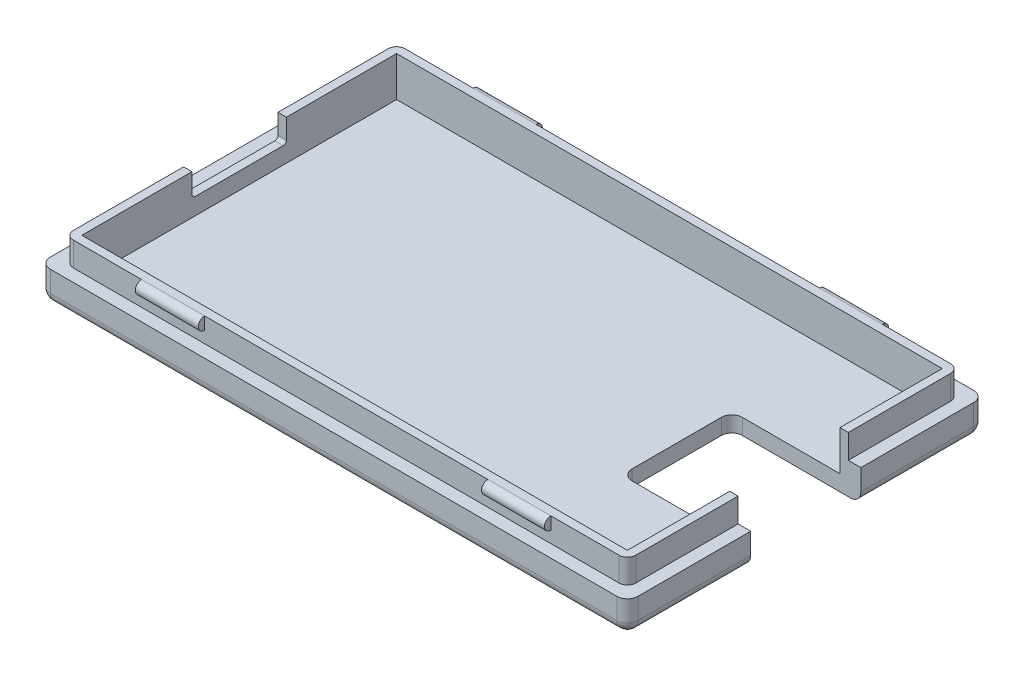
SolidWorks part; units mm, degrees
material "ABS"
ref_plane "Front Plane" through (0, 0, 0) normal (0, 0, 1) x (1, 0, 0)
ref_plane "Top Plane" through (0, 0, 0) normal (0, 1, 0) x (1, 0, 0)
ref_plane "Right Plane" through (0, 0, 0) normal (1, 0, 0) x (0, 0, -1)
sketch "Sketch1" plane through (0, 0, 0) normal (0, 1, 0) x (1, 0, 0)
  line L1 (28, -17) -> (-28, -17)
  line L2 (28, -17) -> (28, 17)
  line L3 (28, 17) -> (-28, 17)
  line L4 (-28, -17) -> (-28, 17)
  line L5 (28, -17) -> (-28, 17) construction
  line L6 (28, 17) -> (-28, -17) construction
  line L7 (26, -15) -> (-26, -15)
  line L8 (26, -15) -> (26, 15)
  line L9 (26, 15) -> (-26, 15)
  line L10 (-26, -15) -> (-26, 15)
  line L11 (26, -15) -> (-26, 15) construction
  line L12 (26, 15) -> (-26, -15) construction
  point P0 (0, 0)
  point P6 (0, 0)
  dimension "D1" = 56
  dimension "D2" = 34
  dimension "D3" = 2
  dimension "D4" = 2
extrude "Base" add sketch "Sketch1" along normal blind 1.5 contours L10 L7 L8 L9 | L4 L1 L2 L3 L7 L10 L9 L8 region at (0, 0, 16.3449) region at (0, 0, 0)
extrude "Boss-Extrude2" add sketch "Sketch1<3>" along normal blind 3 contours L4 L1 L2 L3 L7 L10 L9 L8 region at (0, 0, 16.3449)
sketch "Sketch1<3>" plane through (0, 0, 0) normal (0, 1, 0) x (1, 0, 0) same geometry as "Sketch1"
sketch "Sketch2" plane through (0, 3, 0) normal (0, 1, 0) x (1, 0, 0)
  line L0 (26, 15) -> (26, -15) construction
  line L1 (-26, -15) -> (26, -15) construction
  line L2 (-26, -15) -> (-26, 15) construction
  line L3 (-26, 15) -> (26, 15) construction
  line L4 (26, 15) -> (26, -15)
  line L5 (-26, -15) -> (26, -15)
  line L6 (-26, -15) -> (-26, 15)
  line L7 (-26, 15) -> (26, 15)
  line L8 (-26.8, 15.8) -> (26.8, 15.8)
  line L9 (26.8, 15.8) -> (26.8, -15.8)
  line L10 (-26.8, -15.8) -> (26.8, -15.8)
  line L11 (-26.8, -15.8) -> (-26.8, 15.8)
  dimension "D1" = 0.8
extrude "Wall" add sketch "Sketch2" along normal blind 2.3
sketch "Sketch3" plane through (0, 3, 0) normal (0, 1, 0) x (1, 0, 0)
  line L0 (-28, -17) -> (-28, 17) construction
  line L1 (-28, -10.25) -> (-26.8, -10.25)
  line L2 (-28, -10.25) -> (-28, -6.5)
  line L3 (-28, -6.5) -> (-26.8, -6.5)
  line L4 (-26.8, -10.25) -> (-26.8, -6.5)
  line L5 (-26.8, 15.8) -> (-26.8, -15.8) construction
  line L6 (0, 0) -> (-10.9883, 0) construction
  line L7 (-28, 6.5) -> (-26.8, 6.5)
  line L8 (-26.8, 10.25) -> (-26.8, 6.5)
  line L9 (-28, 10.25) -> (-26.8, 10.25)
  line L10 (-28, 10.25) -> (-28, 6.5)
  dimension "D1" = 13
  dimension "D2" = 20.5
extrude "GrooveForOpen" cut sketch "Sketch3" against normal blind 1
sketch "Sketch4" plane through (0, 0, 0) normal (1, 0, 0) x (0, 0, -1)
  line L0 (15.8, 5.3) -> (15.8, 3) construction
  line L1 (-15.8, 5.3) -> (-15.8, 3) construction
  circle A0 centre (15.8, 4.7) radius 0.6
  circle A1 centre (-15.8, 4.7) radius 0.6
  dimension "D1" = 1.2
extrude "LockPins" add sketch "Sketch4" along normal blind 6 from offset 13.5
mirror "LockPins2" about plane through (0, 0, 0) normal (1, 0, 0) of "LockPins"
fillet "FilletBase" radius 1 8 edges at (0, 0, 17) (28, 0, 0) (0, 0, -17) (-28, 0, 0) (28, 1.5, 17) (-28, 1.5, 17) (-28, 1.5, -17) (28, 1.5, -17)
fillet "FilletInner" radius 0.8 4 edges at (26.8, 4.15, 15.8) (-26.8, 4.15, 15.8) (-26.8, 4.15, -15.8) (26.8, 4.15, -15.8)
sketch "Sketch5" plane through (0, 0, 0) normal (1, 0, 0) x (0, 0, -1)
  line L0 (-15, 5.3) -> (15, 5.3) construction
  line L1 (-4.5, 5.4623) -> (4.5, 5.4623)
  line L2 (-4.5, 5.4623) -> (-4.5, 3.4)
  line L3 (-4.2, 3.1) -> (4.2, 3.1)
  line L4 (4.5, 5.4623) -> (4.5, 3.4)
  arc A0 (4.2, 3.1) -> (4.5, 3.4) centre (4.2, 3.4) ccw
  arc A1 (-4.5, 3.4) -> (-4.2, 3.1) centre (-4.2, 3.4) ccw
  point P4 (0, 5.4623)
  dimension "D2" = 0.3
  dimension "D1" = 9
  dimension "D3" = 2.2
extrude "CutCable" cut sketch "Sketch5" against normal through all
sketch "Sketch7" plane through (0, 0, 0) normal (0, -1, 0) x (1, 0, 0)
  line L0 (28, 16) -> (28, -16) construction
  line L1 (28.0151, -5.25) -> (16.7, -5.25)
  line L2 (28.0151, -5.25) -> (28.0151, 5.25)
  line L3 (28.0151, 5.25) -> (16.7, 5.25)
  line L4 (15.7, -4.25) -> (15.7, 4.25)
  line L5 (28.0151, -5.25) -> (15.7, 5.25) construction
  line L6 (28.0151, 5.25) -> (15.7, -5.25) construction
  arc A0 (16.7, -5.25) -> (15.7, -4.25) centre (16.7, -4.25) cw
  arc A1 (15.7, 4.25) -> (16.7, 5.25) centre (16.7, 4.25) cw
  point P0 (21.8576, 0)
  dimension "D2" = 1
  dimension "D1" = 10.5
  dimension "D4" = 12.3
extrude "CutForConnector" cut sketch "Sketch7" against normal through all
